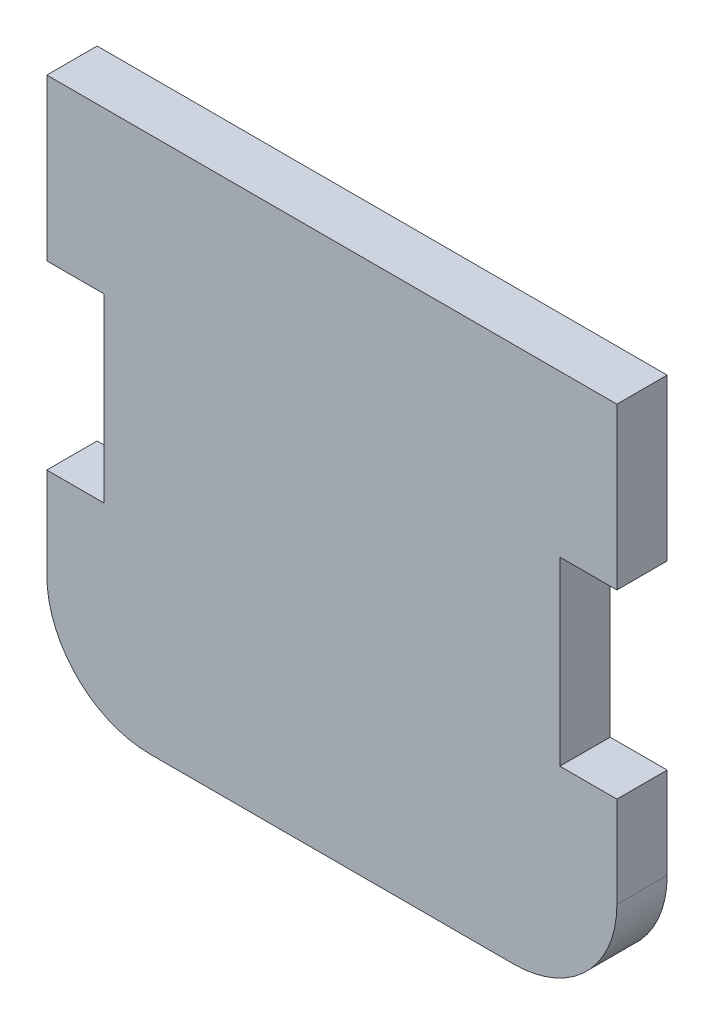
SolidWorks part; units mm, degrees
ref_plane "Front Plane" through (0, 0, 0) normal (0, 0, 1) x (1, 0, 0)
ref_plane "Top Plane" through (0, 0, 0) normal (0, 1, 0) x (1, 0, 0)
ref_plane "Right Plane" through (0, 0, 0) normal (1, 0, 0) x (0, 0, -1)
sketch "Sketch1" plane through (0, 0, 0) normal (0, 0, 1) x (1, 0, 0)
  line L0 (-434.0225, 0) -> (-432.1175, 0) construction
  line L1 (-432.1175, 0) -> (-432.1175, -6.35) construction
  line L3 (-432.1175, -12.7) -> (-432.1175, -6.35) construction
  line L4 (-432.1175, -12.7) -> (-432.1175, -16.4084) construction
  line L9 (-453.7075, 0) -> (-451.8025, 0) construction
  line L10 (-453.7075, -6.35) -> (-453.7075, 0) construction
  line L11 (-453.7075, -6.35) -> (-453.7075, -12.7) construction
  line L12 (-453.7075, -16.4084) -> (-453.7075, -12.7) construction
  line L13 (-436.0291, -20.32) -> (-449.7959, -20.32) construction
  line L14 (-434.0225, 0) -> (-432.1175, 0)
  line L15 (-432.1175, 0) -> (-432.1175, -6.35)
  line L17 (-432.1175, -12.7) -> (-432.1175, -6.35)
  line L18 (-432.1175, -12.7) -> (-432.1175, -16.4084)
  line L23 (-453.7075, 0) -> (-451.8025, 0)
  line L24 (-453.7075, -6.35) -> (-453.7075, 0)
  line L25 (-453.7075, -6.35) -> (-453.7075, -12.7)
  line L26 (-453.7075, -16.4084) -> (-453.7075, -12.7)
  line L27 (-436.0291, -20.32) -> (-449.7959, -20.32)
  line L29 (-451.8025, 0) -> (-434.0225, 0)
  arc A0 (-436.0291, -20.32) -> (-432.1175, -16.4084) centre (-436.0291, -16.4084) ccw construction
  arc A3 (-453.7075, -16.4084) -> (-449.7959, -20.32) centre (-449.7959, -16.4084) ccw construction
  arc A4 (-436.0291, -20.32) -> (-432.1175, -16.4084) centre (-436.0291, -16.4084) ccw
  arc A7 (-453.7075, -16.4084) -> (-449.7959, -20.32) centre (-449.7959, -16.4084) ccw
extrude "Boss-Extrude1" add sketch "Sketch1" along normal blind 1.905 contours L14 L15 L17 L18 A4 L27 A7 L26 L25 L24 L23 L29
sketch "Sketch2" plane through (0, 0, 1.905) normal (0, 0, 1) x (1, 0, 0)
  line L0 (-432.1175, 0) -> (-432.1175, -16.4084) construction
  line L1 (-432.1175, -12.7) -> (-434.0225, -12.7) construction
  line L2 (-432.1175, -12.7) -> (-432.1175, -6.35) construction
  line L3 (-432.1175, -6.35) -> (-434.0225, -6.35) construction
  line L4 (-434.0225, -12.7) -> (-434.0225, -6.35) construction
  line L5 (-434.0225, -12.7) -> (-432.1175, -12.7) construction
  line L14 (-431.8635, -12.954) -> (-434.2765, -12.954)
  line L15 (-434.2765, -12.954) -> (-434.2765, -6.096)
  line L16 (-431.8635, -6.096) -> (-434.2765, -6.096)
  line L17 (-431.8635, -12.954) -> (-431.8635, -6.096)
  line L18 (-442.9125, -1020.32) -> (-442.9125, 48979.68) construction
  line L19 (-436.0291, -20.32) -> (-449.7959, -20.32) construction
  line L20 (-451.8025, -12.7) -> (-451.8025, -6.35) construction
  line L21 (-453.7075, -6.35) -> (-451.8025, -6.35) construction
  line L22 (-453.7075, -12.7) -> (-453.7075, -6.35) construction
  line L23 (-453.7075, -12.7) -> (-451.8025, -12.7) construction
  line L24 (-453.9615, -12.954) -> (-453.9615, -6.096)
  line L25 (-453.9615, -6.096) -> (-451.5485, -6.096)
  line L26 (-451.5485, -12.954) -> (-451.5485, -6.096)
  line L27 (-453.9615, -12.954) -> (-451.5485, -12.954)
  point P18 (-442.9125, -20.32)
  dimension "D1" = 0.254
extrude "Cut-Extrude1" cut sketch "Sketch2" against normal through all
